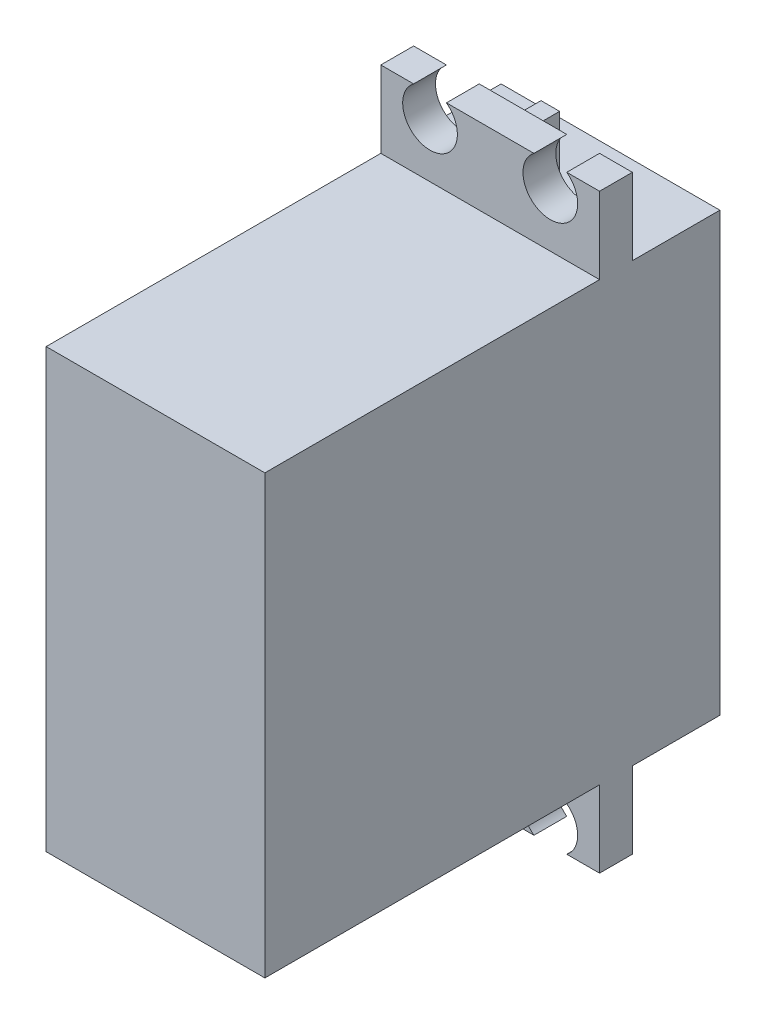
SolidWorks part; units mm, degrees
ref_plane "Front Plane" through (0, 0, 0) normal (0, 0, 1) x (1, 0, 0)
ref_plane "Top Plane" through (0, 0, 0) normal (0, 1, 0) x (1, 0, 0)
ref_plane "Right Plane" through (0, 0, 0) normal (1, 0, 0) x (0, 0, -1)
sketch "Sketch1" plane through (0, 0, 0) normal (0, 0, 1) x (1, 0, 0)
  line L1 (-10, -20) -> (10, -20)
  line L2 (-10, -20) -> (-10, 20)
  line L3 (-10, 20) -> (10, 20)
  line L4 (10, -20) -> (10, 20)
  line L5 (-10, -20) -> (10, 20) construction
  line L6 (-10, 20) -> (10, -20) construction
  point P0 (0, 0)
  dimension "D1" = 20
  dimension "D2" = 40
extrude "Boss-Extrude1" add sketch "Sketch1" along normal blind 41.6
sketch "Sketch2" plane through (0, 0, 0) normal (0, 0, -1) x (-1, 0, 0)
  line L0 (-10, 20) -> (10, 20) construction
  circle A0 centre (0, 10) radius 3
  circle A1 centre (0, 10) radius 1.5
  point P4 (0, 20)
  dimension "D1" = 6
  dimension "D3" = 3
  dimension "D2" = 10
extrude "Boss-Extrude2" add sketch "Sketch2" along normal blind 4
sketch "Sketch3" plane through (0, 0, 0) normal (0, 0, -1) x (-1, 0, 0)
  line L0 (-10, -20) -> (-10, 20) construction
  line L1 (-10, 0) -> (10, 0)
  line L2 (-10, -27) -> (-10, 27)
  line L3 (-10, 27) -> (10, 27)
  line L4 (10, -27) -> (10, 27)
  line L5 (10, 20) -> (10, -20) construction
  line L6 (-10, 20) -> (10, 20) construction
  line L7 (-10, -27) -> (10, -27)
  circle A0 centre (-5.5, 25) radius 2.5
  circle A1 centre (5.5, 25) radius 2.5
  circle A2 centre (5.5, -25) radius 2.5
  circle A3 centre (-5.5, -25) radius 2.5
  point P15 (-10, 0)
  line M6 (-10, -20) -> (10, -20)
  line M8 (10, 20) -> (-10, 20)
  dimension "D3" = 5
  dimension "D1" = 7
  dimension "D2" = 5
  dimension "D4" = 4.5
  dimension "D5" = 4.5
extrude "Boss-Extrude3" add sketch "Sketch3" along normal blind 3 from offset 11 contours A1 L3 A0 L2 L4 M8 | L7 A3 A2 L4 L2 M6 region at (0, -23.0005, 0) region at (0, 23.0005, 0) offset against normal yes
sketch "Sketch5" plane through (0, 0, 8) normal (0, 0, -1) x (-1, 0, 0)
  line L0 (10, 20) -> (-10, 20) construction
  line L1 (-0.85, 26) -> (0.85, 26)
  line L2 (-0.85, 26) -> (-0.85, 20)
  line L3 (-0.85, 20) -> (0.85, 20)
  line L4 (0.85, 26) -> (0.85, 20)
  line L5 (0.85, -20) -> (-0.85, -20)
  line L6 (0.85, -20) -> (0.85, -26)
  line L7 (0.85, -26) -> (-0.85, -26)
  line L8 (-0.85, -20) -> (-0.85, -26)
  line L9 (-10, -20) -> (10, -20) construction
  point P6 (0, 20)
  point P7 (0, 20)
  point P13 (0, -20)
  point P16 (0, -20)
  dimension "D1" = 6
  dimension "D2" = 1.7
  dimension "D3" = 6
  dimension "D4" = 1.7
extrude "Boss-Extrude4" add sketch "Sketch5" along normal blind 2.5
